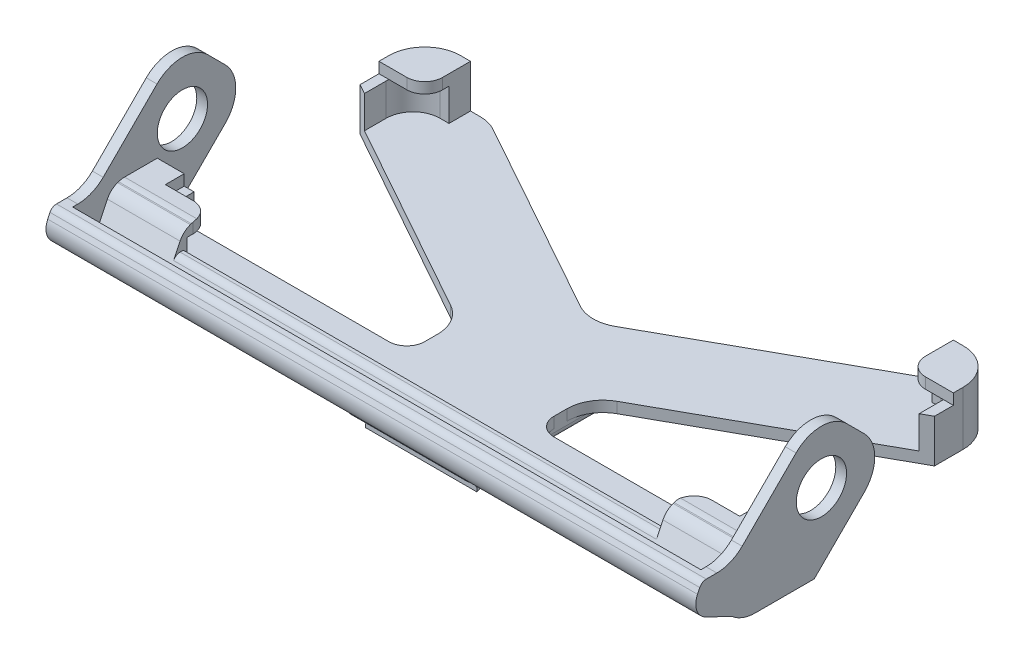
SolidWorks part; units mm, degrees
other "标注1"
sketch "草图28" plane through (-90.5, 42, -81) normal (-0.7789, 0.3736, -0.5038) x (-0.1196, 0.7, 0.7041)
ref_plane "前视基准面" through (0, 0, 0) normal (0, 0, 1) x (1, 0, 0)
ref_plane "上视基准面" through (0, 0, 0) normal (0, 1, 0) x (1, 0, 0)
ref_plane "右视基准面" through (0, 0, 0) normal (1, 0, 0) x (0, 0, -1)
sketch "草图1" plane through (0, 0, 0) normal (0, 1, 0) x (1, 0, 0)
  line L0 (-8, 28.5) -> (8, 28.5)
  line L1 (8, 28.5) -> (15.5, 0)
  line L2 (15.5, 0) -> (-15.5, 0)
  line L3 (-15.5, 0) -> (-8, 28.5)
  line L4 (0, -32.0604) -> (0, 1570.9599) construction
  point P6 (0, 28.5)
  point P8 (0, 0)
  dimension "D1" = 31
  dimension "D2" = 16
  dimension "D3" = 28.5
extrude "凸台-拉伸1" add sketch "草图1" along normal blind 4
fillet "圆角1" radius 3 2 edges at (11.75, 4, -14.25) (-11.75, 4, -14.25) profile chamfer
sketch "草图2" plane through (0, 4, 0) normal (0, 1, 0) x (1, 0, 0)
  line L0 (-4.8979, 28.5) -> (-9.3158, 23.5)
  line L1 (-15.5, 0) -> (-8, 28.5) construction
  line L2 (-9.3158, 23.5) -> (-9.3158, 28.5)
  line L3 (-9.3158, 28.5) -> (-4.8979, 28.5)
  line L4 (0, -1000) -> (0, 49000) construction
  line L5 (-12.3979, 0) -> (12.3979, 0) construction
  line L6 (9.3158, 28.5) -> (4.8979, 28.5)
  line L7 (9.3158, 23.5) -> (9.3158, 28.5)
  line L8 (4.8979, 28.5) -> (9.3158, 23.5)
  point P11 (0, 0)
  dimension "D1" = 5
extrude "切除-拉伸1" cut sketch "草图2" against normal through all
sketch "草图3" plane through (0, 4, 0) normal (0, 1, 0) x (1, 0, 0)
  line L0 (0, 9.5574) -> (0, 0) construction
  line L1 (-4.8979, 28.5) -> (-12.3979, 0) construction
  circle A0 centre (0, 9.5574) radius 9.5574
extrude "凸台-拉伸2" add sketch "草图3" along normal blind 3 contours A0
sketch "草图5" plane through (0, 0, 0) normal (0, -1, 0) x (1, 0, 0)
  line L0 (-7.5, -24) -> (7.5, -24)
  line L1 (7.5, -24) -> (7.5, -22)
  line L2 (7.5, -22) -> (6, -22)
  line L3 (6, -22) -> (6, -4)
  line L4 (6, -4) -> (-6, -4)
  line L5 (-6, -4) -> (-6, -22)
  line L6 (-6, -22) -> (-7.5, -22)
  line L7 (-7.5, -22) -> (-7.5, -24)
  line L8 (-6, -22) -> (6, -22) construction
  line L9 (0, -1000) -> (0, 49000) construction
  line L10 (-15.5, 0) -> (15.5, 0) construction
  point P9 (0, -4)
  point P12 (0, -24)
  dimension "D1" = 12
  dimension "D2" = 15
  dimension "D3" = 4
  dimension "D4" = 2
  dimension "D5" = 20
extrude "切除-拉伸2" cut sketch "草图5" against normal blind 2
sketch "草图7" plane through (0, 7, 0) normal (0, 1, 0) x (1, 0, 0)
  circle A0 centre (0, 9.5574) radius 2
  dimension "D1" = 4
extrude "切除-拉伸3" cut sketch "草图7" against normal through all
sketch "草图8" plane through (0, 0, 0) normal (1, 0, 0) x (0, 0, -1)
  line L0 (7.5574, 5) -> (5.5574, 3)
  line L1 (7.5574, 7) -> (7.5574, 2) construction
  line L3 (5.5574, 3) -> (9.5574, 3) construction
  line L4 (7.5574, 5) -> (9.5574, 5)
  line L5 (9.5574, -993) -> (9.5574, 49007) construction
  line L6 (19.1147, 7) -> (0, 7) construction
  line L7 (11.5574, 7) -> (7.5574, 7) construction
  line L8 (22, 2) -> (4, 2) construction
  line L9 (9.5574, 2) -> (9.5574, 5)
  line L10 (5.5574, 3) -> (5.5574, 2)
  line L11 (5.5574, 2) -> (9.5574, 2)
  point P13 (9.5574, 7)
  dimension "D1" = 2
  dimension "D2" = 4
  dimension "D3" = 1
revolve "切除-旋转1" cut sketch "草图8" angle 360 about L5
fillet "圆角2" radius 1 4 edges at (-7.5, 1, -22) (-7.5, 1, -24) (7.5, 1, -24) (7.5, 1, -22)
sketch "草图9" plane through (0, 4, 0) normal (0, 1, 0) x (1, 0, 0)
  line L0 (-18, -4) -> (18, -4)
  line L1 (-12.3979, 0) -> (0, 0) construction
  line L2 (-18, -4) -> (-18, 28.5)
  line L3 (-18, 28.5) -> (18, 28.5) construction
  line L4 (18, 28.5) -> (18, -4)
  line L5 (4.8979, 28.5) -> (-4.8979, 28.5) construction
  line L6 (-18, 28.5) -> (-18, 80.5)
  line L7 (-18, 80.5) -> (18, 80.5)
  line L8 (18, 80.5) -> (18, 28.5)
  circle A0 centre (0, 9.5574) radius 9.5574
  circle A1 centre (0, 9.5574) radius 9.5574 construction
  point P4 (0, -4)
  dimension "D1" = 4
  dimension "D2" = 36
  dimension "D3" = 52
extrude "凸台-拉伸4" add sketch "草图9" along normal up to surface (3 mm away) up to face at (0, 7, -7.5574)
sketch "草图10" plane through (0, 7, 0) normal (0, 1, 0) x (1, 0, 0)
  line L1 (-80, -4) -> (80, -4)
  line L2 (-80, -4) -> (-80, 81)
  line L3 (-80, 81) -> (80, 81)
  line L4 (80, -4) -> (80, 81)
  line L5 (-80, -4) -> (80, 81) construction
  line L6 (-80, 81) -> (80, -4) construction
  line L7 (0, 0) -> (0, 38.5) construction
  line L8 (-18, -4) -> (18, -4) construction
  point P0 (0, 38.5)
  dimension "D1" = 160
  dimension "D2" = 85
extrude "凸台-拉伸5" add sketch "草图10" along normal blind 3
sketch "草图11" plane through (0, 10, 0) normal (0, 1, 0) x (1, 0, 0)
  line L0 (-80, -4) -> (80, -4) construction
  line L1 (-80, 81) -> (-77.25, 81)
  line L2 (-80, 81) -> (-80, -4)
  line L3 (-80, -4) -> (-77.25, -4)
  line L4 (-77.25, 81) -> (-77.25, -4)
  line L6 (80, 81) -> (77.25, 81)
  line L7 (80, 81) -> (80, -4)
  line L8 (80, -4) -> (77.25, -4)
  line L9 (77.25, 81) -> (77.25, -4)
  dimension "D1" = 2.75
  dimension "D2" = 2.75
extrude "凸台-拉伸6" add sketch "草图11" along normal blind 9
sketch "草图12" plane through (0, 10, 0) normal (0, 1, 0) x (1, 0, 0)
  line L1 (-77.25, 81) -> (-67.25, 81)
  line L2 (-77.25, 81) -> (-77.25, 75)
  line L3 (-77.25, 75) -> (-67.25, 75)
  line L4 (-67.25, 81) -> (-67.25, 75)
  line L5 (77.25, 81) -> (67.25, 81)
  line L6 (77.25, 81) -> (77.25, 75)
  line L7 (77.25, 75) -> (67.25, 75)
  line L8 (67.25, 81) -> (67.25, 75)
  line L9 (80, -4) -> (67.25, -4)
  line L10 (80, -4) -> (80, 2)
  line L11 (80, 2) -> (67.25, 2)
  line L12 (67.25, -4) -> (67.25, 2)
  line L13 (-80, -4) -> (-67.25, -4)
  line L14 (-80, -4) -> (-80, 2)
  line L15 (-80, 2) -> (-67.25, 2)
  line L16 (-67.25, -4) -> (-67.25, 2)
  line L17 (-67.25, 75) -> (67.25, 75) construction
  line L18 (-67.25, 75) -> (-67.25, 2) construction
  line L19 (-67.25, 2) -> (67.25, 2) construction
  line L20 (67.25, 75) -> (67.25, 2) construction
  dimension "D1" = 6
  dimension "D2" = 6
  dimension "D3" = 10
  dimension "D4" = 10
extrude "凸台-拉伸7" add sketch "草图12" along normal blind 9
sketch "草图13" plane through (0, 19, 0) normal (0, 1, 0) x (1, 0, 0)
  line L0 (-67.25, 81) -> (-80, 81) construction
  line L9 (-67.25, 68.25) -> (-80, 68.25)
  line L10 (-67.25, 68.25) -> (-67.25, 81)
  line L11 (-67.25, 81) -> (-80, 81)
  line L12 (-80, 68.25) -> (-80, 81)
  line L13 (-67.25, 68.25) -> (-80, 81) construction
  line L14 (-67.25, 81) -> (-80, 68.25) construction
  line L15 (-80, 81) -> (-80, -4) construction
  line L16 (-67.25, -4) -> (-67.25, 2) construction
  line L17 (-67.25, 8.75) -> (-80, 8.75)
  line L18 (-67.25, 8.75) -> (-67.25, -4)
  line L19 (-67.25, -4) -> (-80, -4)
  line L20 (-80, 8.75) -> (-80, -4)
  line L21 (-67.25, 8.75) -> (-80, -4) construction
  line L22 (-67.25, -4) -> (-80, 8.75) construction
  line L23 (67.25, 68.25) -> (80, 68.25)
  line L24 (67.25, 68.25) -> (67.25, 81)
  line L25 (67.25, 81) -> (80, 81)
  line L26 (80, 68.25) -> (80, 81)
  line L27 (67.25, 68.25) -> (80, 81) construction
  line L28 (67.25, 81) -> (80, 68.25) construction
  line L29 (67.25, 8.75) -> (80, 8.75)
  line L30 (67.25, 8.75) -> (67.25, -4)
  line L31 (67.25, -4) -> (80, -4)
  line L32 (80, 8.75) -> (80, -4)
  line L33 (67.25, 8.75) -> (80, -4) construction
  line L34 (67.25, -4) -> (80, 8.75) construction
  line L35 (67.25, 2) -> (67.25, -4) construction
  line L36 (67.25, 81) -> (67.25, 75) construction
  line L39 (-67.25, 75) -> (-67.25, 81) construction
  point P0 (-73.625, 74.625)
  point P14 (-73.625, 2.375)
  point P21 (73.625, 74.625)
  point P28 (73.625, 2.375)
extrude "凸台-拉伸8" add sketch "草图13" along normal blind 3
sketch "草图14" plane through (-80, 0, 0) normal (-1, 0, 0) x (0, 0, 1)
  line L0 (14.1903, 14.4943) -> (37.8859, 46.7204)
  line L1 (37.8859, 46.7204) -> (-50.1764, 168.1495)
  line L2 (17.1092, 75.3694) -> (-45.4198, 55.1366)
  line L3 (-45.4198, 55.1366) -> (-43.0956, 17.5376)
  dimension "D1" = 40
  dimension "D2" = 37.6707
  dimension "D3" = 150
  dimension "D4" = 65.7209
  dimension "D5" = 107.723
  dimension "D6" = 35.3897
sketch "草图21" plane through (0, 19, 0) normal (0, 1, 0) x (1, 0, 0)
  line L4 (-920, 38.5) -> (49080, 38.5) construction
  line L5 (80, 8.75) -> (80, 68.25) construction
  line L7 (0, -1000) -> (0, 49000) construction
  line L17 (-62, 81) -> (62, 81)
  line L19 (-67.25, 81) -> (-62, 81) construction
  line L21 (-80, 63) -> (-80, 68.25) construction
  line L27 (-18, 80.5) -> (-18, -4) construction
  line L30 (67.25, 81) -> (-67.25, 81) construction
  line L31 (62, 81) -> (0, 46.5)
  line L32 (0, 46.5) -> (-62, 81)
  line L33 (-80, 63) -> (-18, 28.5)
  line L34 (-80, 68.25) -> (-80, 8.75) construction
  line L35 (-18, 28.5) -> (-18, 14)
  line L36 (-18, 14) -> (-80, 14)
  line L37 (-80, 14) -> (-80, 63)
  line L40 (18, 14) -> (80, 14)
  line L41 (18, 28.5) -> (18, 14)
  line L42 (80, 63) -> (18, 28.5)
  line L43 (80, 14) -> (80, 63)
  line L44 (-18, 28.5) -> (0, 46.5) construction
  line L45 (18, 28.5) -> (0, 46.5) construction
  line L46 (4.8979, 28.5) -> (-4.8979, 28.5) construction
  point P10 (80, 38.5)
  point P22 (-18, 28.6634)
  point P24 (0, 0)
extrude "切除-拉伸7" cut sketch "草图21" against normal through all
fillet "圆角3" radius 7.5 4 edges at (-77.25, 14.5, -2) (77.25, 14.5, -2) (77.25, 14.5, -75) (-77.25, 14.5, -75)
sketch "草图22" plane through (80, 0, 0) normal (1, 0, 0) x (0, 0, -1)
  line L0 (-4, 7) -> (14, 7)
  line L2 (14, 7) -> (14, 22)
  line L3 (14, 22) -> (-4, 22)
  line L4 (-4, 22) -> (-4, 7)
  point P3 (14, 7)
  point P7 (0, 0)
extrude "凸台-拉伸9" add sketch "草图22" along normal blind 7.5
sketch "草图23" plane through (87.5, 0, 0) normal (1, 0, 0) x (0, 0, -1)
  line L0 (-4, 7) -> (14, 7) construction
  line L1 (14, 7) -> (14, 22) construction
  line L2 (-4, 7) -> (19, 7)
  line L3 (19, 7) -> (40, 28)
  line L7 (-4, 22) -> (21, 47)
  line L8 (21, 47) -> (40, 28)
  line L9 (14, 22) -> (-4, 22) construction
  line L10 (-4, 7) -> (-4, 22)
  line L12 (21, 28) -> (30.5, 37.5) construction
  line L13 (21, 28) -> (11.5, 37.5) construction
  circle A0 centre (21, 28) radius 7
  point P9 (0, 0)
  point P11 (0, 0)
  point P13 (0, 0)
  point P19 (17.2294, 7)
  point P20 (0, 0)
  dimension "D2" = 14
  dimension "D1" = 21
  dimension "D3" = 45
extrude "凸台-拉伸10" add sketch "草图23" along normal blind 3
mirror "镜向1" about plane through (0, 0, 0) normal (1, 0, 0) of "凸台-拉伸10", "凸台-拉伸9"
sketch "草图25" plane through (0, 0, 0) normal (1, 0, 0) x (0, 0, -1)
  line L0 (21, 28) -> (-5.6667, 18.5719) construction
  line L2 (-12.3333, 16.2149) -> (-3.3096, 11.9052) construction
  line L3 (-12.3333, 16.2149) -> (-8.0237, 25.2386)
  line L4 (-8.0237, 25.2386) -> (1, 20.9289) construction
  line L5 (-3.3096, 11.9052) -> (1, 20.9289) construction
  line L6 (-12.3333, 16.2149) -> (1, 20.9289) construction
  line L7 (-8.0237, 25.2386) -> (-3.3096, 11.9052) construction
  line L8 (-15.6667, 15.0364) -> (-2.1311, 8.5719) construction
  line L9 (-15.6667, 15.0364) -> (-9.2022, 28.5719) construction
  line L10 (-9.2022, 28.5719) -> (4.3333, 22.1074) construction
  line L11 (-2.1311, 8.5719) -> (4.3333, 22.1074) construction
  line L12 (-15.6667, 15.0364) -> (4.3333, 22.1074) construction
  line L13 (-9.2022, 28.5719) -> (-2.1311, 8.5719) construction
  line L14 (1, 20.9289) -> (4.3333, 22.1074)
  line L15 (-5.6667, 18.5719) -> (2.9526, 36.6193) construction
  line L16 (2.9526, 36.6193) -> (21, 28) construction
  line L17 (1, 16.4171) -> (1, 20.9289) construction
  line L19 (-4, 12.235) -> (-12.3333, 16.2149)
  line L20 (-15.6667, 15.0364) -> (1.1602, 7)
  line L21 (1, 16.4171) -> (1, 7)
  line L22 (-4, 22) -> (-4, 7) construction
  line L23 (1, 7) -> (1.1602, 7)
  line L24 (-4, 12.235) -> (-3.3096, 11.9052)
  line L25 (-3.3096, 11.9052) -> (-1.1548, 16.4171)
  line L26 (-1.1548, 16.4171) -> (1, 16.4171)
  line L27 (-15.6667, 15.0364) -> (-12.3409, 22)
  line L28 (-12.3409, 22) -> (-6.8787, 22)
  line L29 (-6.8787, 22) -> (-8.0237, 25.2386)
  line L31 (-4, 7) -> (19, 7) construction
  circle A0 centre (21, 28) radius 7 construction
  point P20 (2, 10)
  dimension "D1" = 20
  dimension "D2" = 45
  dimension "D3" = 10
  dimension "D4" = 10
  dimension "D5" = 15
  dimension "D6" = 20
  dimension "D7" = 1
extrude "凸台-拉伸11" add sketch "草图25" against normal up to surface and the other way up to surface
sketch "草图26" plane through (67.25, 0, 0) normal (1, 0, 0) x (0, 0, -1)
  line L1 (-4, 9.4645) -> (-15.6667, 15.0364)
  line L2 (-15.6667, 15.0364) -> (-12.3409, 22)
  line L3 (-4, 22) -> (-4, 7) construction
  line L5 (-12.3409, 22) -> (-4, 22)
  line L6 (-4, 22) -> (-4, 9.4645)
  line L7 (-15.6667, 15.0364) -> (-12.3409, 22) construction
  line L8 (-15.6667, 15.0364) -> (-4, 9.4645) construction
  point P0 (-4, 22)
extrude "凸台-拉伸12" add sketch "草图26" along normal up to surface (23.25 mm away) up to face at (90.5, 22.2, -14.4)
sketch "草图27" plane through (-67.25, 0, 0) normal (-1, 0, 0) x (0, 0, 1)
  line L1 (4, 9.4645) -> (15.6667, 15.0364)
  line L2 (15.6667, 15.0364) -> (12.3409, 22)
  line L3 (12.3409, 22) -> (4, 22)
  line L4 (4, 22) -> (4, 9.4645)
  line L5 (15.6667, 15.0364) -> (4, 9.4645) construction
  line L6 (4, 22) -> (4, 7) construction
  point P0 (4, 22)
extrude "凸台-拉伸13" add sketch "草图27" along normal up to surface (23.25 mm away) up to face at (-90.5, 28, -28)
sketch "草图24" plane through (0, 0, 0) normal (1, 0, 0) x (0, 0, -1)
  line L0 (21, 28) -> (-5.6667, 18.5719) construction
  line L2 (-12.3333, 16.2149) -> (-3.3096, 11.9052)
  line L3 (-12.3333, 16.2149) -> (-8.0237, 25.2386)
  line L4 (-8.0237, 25.2386) -> (1, 20.9289) construction
  line L5 (-3.3096, 11.9052) -> (1, 20.9289)
  line L6 (-12.3333, 16.2149) -> (1, 20.9289) construction
  line L7 (-8.0237, 25.2386) -> (-3.3096, 11.9052) construction
  line L13 (-8.0237, 25.2386) -> (-9.3207, 29.076)
  line L15 (-5.6667, 18.5719) -> (2.9526, 36.6193) construction
  line L16 (2.9526, 36.6193) -> (21, 28) construction
  line L17 (-12.3333, 16.2149) -> (-3.3096, 11.9052) construction
  line L28 (-9.3207, 29.076) -> (8.4491, 23.5626)
  line L29 (8.4491, 23.5626) -> (1, 20.9289)
  point P20 (2, 10)
  dimension "D1" = 20
  dimension "D2" = 45
  dimension "D3" = 10
  dimension "D4" = 10
  dimension "D6" = 20
extrude "切除-拉伸10" cut sketch "草图24" against normal up to surface and the other way up to surface
fillet "圆角4" radius 10 17 edges at (80, 14.5, -81) (-80, 14.5, -81) (-54.25, 7, 4) (54.25, 7, 4) (62, 8.5, -81) (-62, 8.5, -81) (18, 8.5, -28.5) (-18, 8.5, -28.5) (0, 7, -46.5) (89, 22, 4) (89, 28, -40) (89, 47, -21) (-89, 22, 4) (-89, 47, -21) (-89, 28, -40) (90.5, 8.2322, 4) (-90.5, 8.2322, 4)
fillet "圆角5" radius 5 11 edges at (-18, 8.5, -14) (18, 8.5, -14) (0, 15.0364, 15.6667) (-67.25, 20.5, -8.75) (67.25, 20.5, -8.75) (67.25, 20.5, -68.25) (-67.25, 20.5, -68.25) (77.375, 20.9289, -1) (77.375, 22, -4.0294) (-77.375, 20.9289, -1) (-77.375, 22, -4.0294)
fillet "圆角6" radius 2 9 edges at (-18, 5.5, -56.5161) (18, 5.5, -56.5161) (18, 4, -26.2581) (0, 4, 4) (-18, 4, -26.2581) (-18, 6.7322, 4) (18, 6.7322, 4) (0, 22, 12.3409) (0, 16.4171, 1.1548)
equation "\"length\"= 150"
equation "\"width\"= 75"
equation "\"thick\" =9"
equation "\"D1@草图10\" = \"length\" + 10"
equation "\"D2@草图10\"= \"width\" + 10"
equation "\"D1@凸台-拉伸6\"=\"thick\""
equation "\"D1@凸台-拉伸7\"=\"thick\""
